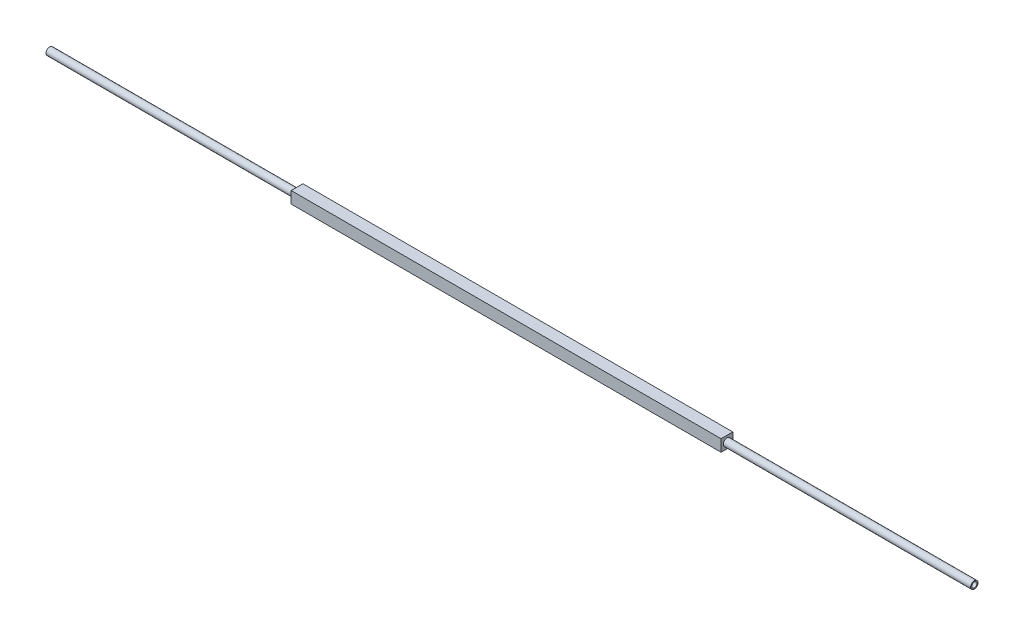
SolidWorks part; units mm, degrees
material "Hexcel AS4C (3000 Filaments)"
ref_plane "Front Plane" through (0, 0, 0) normal (0, 0, 1) x (1, 0, 0)
ref_plane "Top Plane" through (0, 0, 0) normal (0, 1, 0) x (1, 0, 0)
ref_plane "Right Plane" through (0, 0, 0) normal (1, 0, 0) x (0, 0, -1)
sketch "Sketch1" plane through (0, 0, 0) normal (1, 0, 0) x (0, 0, -1)
  line L1 (0, 0) -> (6.35, 0)
  line L2 (0, 0) -> (0, 6.35)
  line L3 (0, 6.35) -> (6.35, 6.35)
  line L4 (6.35, 0) -> (6.35, 6.35)
  circle A0 centre (3.175, 3.175) radius 1.397
  dimension "D3" = 2.794
  dimension "D1" = 6.35
  dimension "D2" = 6.35
extrude "Boss-Extrude1" add sketch "Sketch1" along normal blind 116.205 and the other way blind 116.205
sketch "Sketch3" plane through (0, 0, 0) normal (1, 0, 0) x (0, 0, -1)
  circle A0 centre (3.175, 3.175) radius 1.397 construction
  circle A1 centre (3.175, 3.175) radius 1.397
  circle A2 centre (3.175, 3.175) radius 1.9939
  dimension "D1" = 3.9878
extrude "Boss-Extrude3" add sketch "Sketch3" along normal blind 249.936 and the other way blind 249.936
